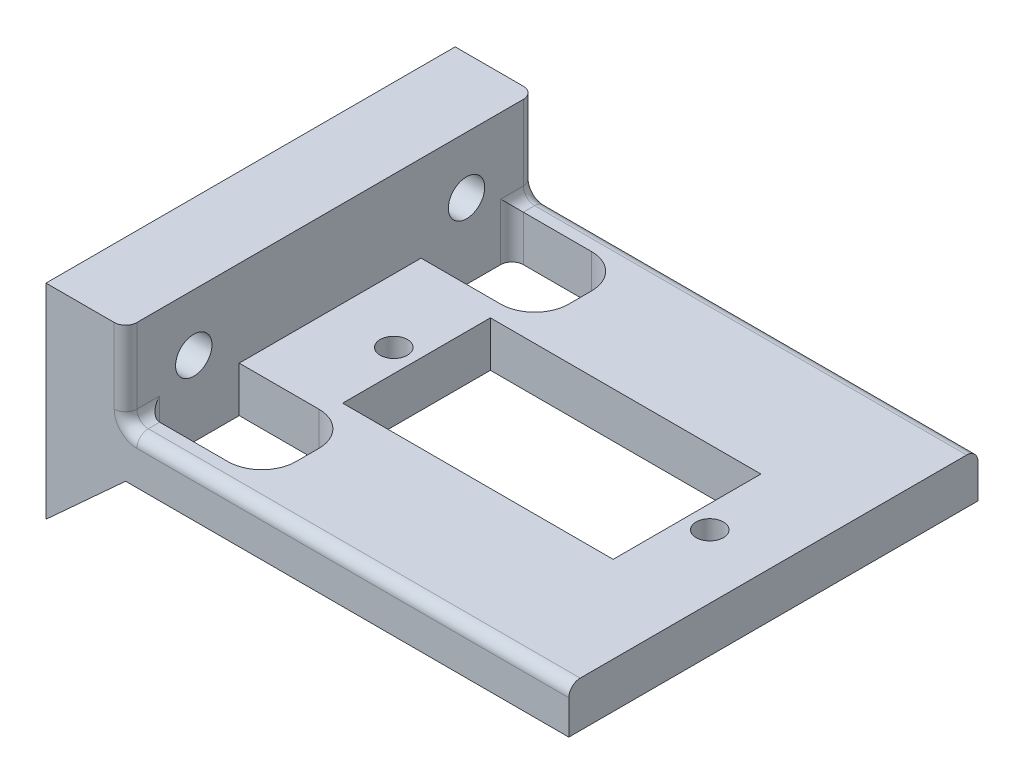
SolidWorks part; units mm, degrees
ref_plane "Front Plane" through (0, 0, 0) normal (0, 0, 1) x (1, 0, 0)
ref_plane "Top Plane" through (0, 0, 0) normal (0, 1, 0) x (1, 0, 0)
ref_plane "Right Plane" through (0, 0, 0) normal (1, 0, 0) x (0, 0, -1)
sketch "Servo_shelf_profile" plane through (0, 0, 0) normal (0, 1, 0) x (1, 0, 0)
  line L1 (-21, -18) -> (25, -18)
  line L2 (-21, -18) -> (-21, 18)
  line L3 (-21, 18) -> (25, 18)
  line L4 (25, -18) -> (25, 18)
  dimension "D1" = 46
  dimension "D2" = 36
  dimension "D3" = 25
  dimension "D4" = 18
extrude "Servo_shelf" add sketch "Servo_shelf_profile" along normal blind 4 from offset 21.4
sketch "Rear_clamping_block_profile" plane through (0, 0, 0) normal (0, 0, 1) x (1, 0, 0)
  line L1 (-21, 23) -> (-14, 23)
  line L2 (-21, 23) -> (-21, 33)
  line L3 (-21, 33) -> (-14, 33)
  line L4 (-14, 23) -> (-14, 33)
  dimension "D1" = 7
  dimension "D2" = 10
  dimension "D3" = 14
  dimension "D4" = 23
extrude "Rear_clamping_block" add sketch "Rear_clamping_block_profile" along normal blind 36 from offset 18 offset against normal yes
sketch "Servo_body_window_profile" plane through (0, 0, 0) normal (0, 1, 0) x (1, 0, 0)
  line L1 (-6.4, -6.5) -> (17.4, -6.5)
  line L2 (-6.4, -6.5) -> (-6.4, 6.5)
  line L3 (-6.4, 6.5) -> (17.4, 6.5)
  line L4 (17.4, -6.5) -> (17.4, 6.5)
  dimension "D1" = 23.8
  dimension "D2" = 13
  dimension "D3" = 17.4
  dimension "D4" = 6.5
extrude "Servo_body_window" cut sketch "Servo_body_window_profile" along normal through all from offset 20.4
sketch "Yaw_servo_M2_fasteners_profile" plane through (0, 0, 0) normal (0, 1, 0) x (1, 0, 0)
  circle A0 centre (-9, 0) radius 1.3
  circle A1 centre (20, 0) radius 1.3
  dimension "D1" = 2.6
  dimension "D2" = 2.6
  dimension "D3" = 20
  dimension "D4" = 9
extrude "Yaw_servo_M2_fasteners_SUPERSEDED_owned_servo" [suppressed] cut sketch "Yaw_servo_M2_fasteners_profile" along normal through all from offset 20.4
sketch "Left_nut_access_profile" plane through (0, 0, 0) normal (0, 1, 0) x (1, 0, 0)
  line L1 (-14, 8) -> (-4, 8)
  line L2 (-14, 8) -> (-14, 16)
  line L3 (-14, 16) -> (-4, 16)
  line L4 (-4, 8) -> (-4, 16)
  dimension "D1" = 10
  dimension "D2" = 8
  dimension "D3" = 4
  dimension "D4" = 8
extrude "Left_nut_access" cut sketch "Left_nut_access_profile" along normal through all from offset 20
sketch "Right_nut_access_profile" plane through (0, 0, 0) normal (0, 1, 0) x (1, 0, 0)
  line L1 (-14, -16) -> (-4, -16)
  line L2 (-14, -16) -> (-14, -8)
  line L3 (-14, -8) -> (-4, -8)
  line L4 (-4, -16) -> (-4, -8)
  dimension "D1" = 10
  dimension "D2" = 8
  dimension "D3" = 4
  dimension "D4" = 8
extrude "Right_nut_access" cut sketch "Right_nut_access_profile" along normal through all from offset 20
sketch "Rear_clamping_M3_profile" plane through (0, 0, 0) normal (1, 0, 0) x (0, 0, -1)
  circle A0 centre (12, 28) radius 1.6
  circle A1 centre (-12, 28) radius 1.6
  dimension "D1" = 3.2
  dimension "D2" = 3.2
  dimension "D3" = 12
  dimension "D4" = 12
  dimension "D5" = 28
extrude "Rear_clamping_M3_holes" cut sketch "Rear_clamping_M3_profile" along normal blind 11 from offset 25 offset against normal yes
fillet "Fillet1" radius 3 4 edges at (-4, 23.4, 16) (-4, 23.4, 8) (-4, 23.4, -16) (-4, 23.4, -8)
fillet "Fillet2" radius 1 8 edges at (-14, 25.4, -17) (-14, 25.4, 17) (-14, 23.4, 16) (-14, 23.4, -16) (-14, 29.2, 18) (5.5, 25.4, 18) (-14, 29.2, -18) (5.5, 25.4, -18)
sketch "Sketch1" plane through (0, 0, -18) normal (0, 0, -1) x (-1, 0, 0)
  line L0 (14, 21.4) -> (21, 15)
  line L1 (21, 15) -> (21, 21.4)
  line L2 (21, 21.4) -> (14, 21.4)
extrude "Boss-Extrude1" add sketch "Sketch1" against normal up to surface (36 mm away) contours L0 L1 L2 up to face at (-5.0592, 26.2265, 18)
sketch "Owned_SG90_M2_ear_holes_profile" plane through (0, 0, 0) normal (0, 1, 0) x (1, 0, 0)
  circle A0 centre (-8.4, 0) radius 1.2
  circle A1 centre (19.4, 0) radius 1.2
  dimension "D1" = 2.4
  dimension "D2" = 2.4
  dimension "D3" = 19.4
  dimension "D4" = 8.4
extrude "Owned_SG90_M2_ear_holes" cut sketch "Owned_SG90_M2_ear_holes_profile" along normal through all from offset 20.4
